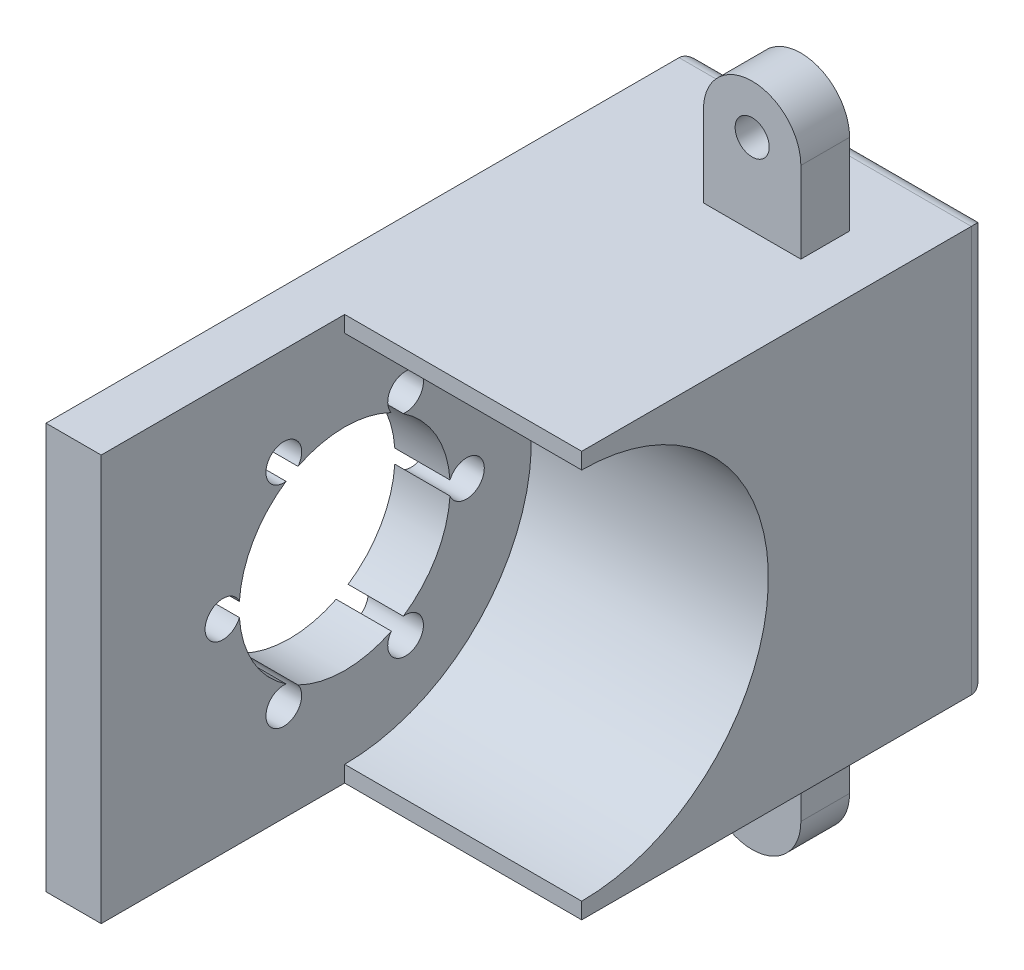
SolidWorks part; units mm, degrees
ref_plane "前视基准面" through (0, 0, 0) normal (0, 0, 1) x (1, 0, 0)
ref_plane "上视基准面" through (0, 0, 0) normal (0, 1, 0) x (1, 0, 0)
ref_plane "右视基准面" through (0, 0, 0) normal (1, 0, 0) x (0, 0, -1)
sketch "草图1" plane through (0, 0, 0) normal (0, 0, 1) x (1, 0, 0)
  line L9 (-11.5, 12.5) -> (11.5, 12.5)
  line L10 (-11.5, 12.5) -> (-11.5, -12.5)
  line L11 (-11.5, -12.5) -> (11.5, -12.5)
  line L12 (11.5, 12.5) -> (11.5, -12.5)
  line L13 (0, -12.5) -> (0, 12.5) construction
  line L14 (-11.5, 0) -> (11.5, 0) construction
  point P0 (0, 0)
  dimension "D1" = 23
  dimension "D2" = 25
extrude "凸台-拉伸1" add sketch "草图1" against normal blind 25 contours L12 L9 L10 L11 region at (0, 0, 0)
ref_axis "基准轴2" through (11.5, 0, 0) along (-1, 0, 0)
sketch "草图2" plane through (0, 0, 0) normal (0, 0, 1) x (1, 0, 0)
  line L0 (11.5, 0) -> (-11.5, 0) construction
  line L1 (11.5, 12.5) -> (11.5, -12.5) construction
  line L2 (11.5, 12.5) -> (11.5, -12.5) construction
  line L3 (11.5, 0) -> (11.5, -11.5)
  line L4 (11.5, -11.5) -> (-8.1, -11.5)
  line L9 (-8.1, -11.5) -> (-8.1, 0)
  line L10 (11.5, 0) -> (-8.1, 0)
  dimension "D1" = 11.5
  dimension "D2" = 19.6
revolve "切除-旋转2" cut sketch "草图2" angle 360 about axis through (11.5, 0, 0) along (-1, 0, 0)
ref_plane "基准面1" through (0, 0, 0) normal (0, 0, 1) x (1, 0, 0)
sketch "草图4" plane through (0, 0, 0) normal (0, 0, 1) x (1, 0, 0)
  line L0 (-8.1, 12.5) -> (-8.1, -12.5)
  line L1 (-11.5, 12.5) -> (11.5, 12.5) construction
  line L2 (-8.1, -12.5) -> (-11.5, -12.5)
  line L3 (-11.5, -12.5) -> (-11.5, 12.5)
  line L4 (-11.5, 12.5) -> (-8.1, 12.5)
  line L5 (-8.1, -11.5) -> (-8.1, 11.5) construction
  line L6 (-8.1, -11.5) -> (-8.1, 10.9) construction
  dimension "D1" = 25
extrude "凸台-拉伸2" add sketch "草图4" along normal blind 15
ref_plane "基准面2" through (-8.1, 0, 0) normal (1, 0, 0) x (0, 0, -1)
sketch "草图6" plane through (-8.1, 0, 0) normal (1, 0, 0) x (0, 0, -1)
  line L0 (0, 0) -> (7.5, 0) construction
  circle A0 centre (0, 0) radius 7.5 construction
  circle A1 centre (7.5, 0) radius 1.1
  circle A2 centre (3.75, -6.4952) radius 1.1
  circle A3 centre (-3.75, -6.4952) radius 1.1
  circle A5 centre (0, 0) radius 6.5
  circle A6 centre (-7.5, 0) radius 1.1
  circle A7 centre (-3.75, 6.4952) radius 1.1
  circle A8 centre (3.75, 6.4952) radius 1.1
  point P12 (0, 0)
  dimension "D1" = 15
  dimension "D2" = 2.2
  dimension "D5" = 13
  dimension "D3" = 6
extrude "切除-拉伸1" cut sketch "草图6" against normal blind 4 contours A7 | A6 | A8 | A1 | A3 | A2 | A5 region at (-8.1, 0, -7.5159) region at (-8.1, 6.509, -3.758) region at (-8.1, -6.509, -3.758) region at (-8.1, 6.509, 3.758) region at (-8.1, -6.509, 3.758) region at (-8.1, 0, 7.5159)
sketch "草图8" plane through (0, 0, -25) normal (0, 0, -1) x (-1, 0, 0)
  line L0 (11.5, -12.5) -> (-11.5, -12.5) construction
  line L1 (0, -1026.5) -> (0, -20.5) construction
  line L2 (11.5, 0) -> (2.7493, 0) construction
  line L3 (3, 17.5) -> (3, 12.5)
  line L5 (-3, -17.5) -> (-3, -12.5)
  line L6 (-3, -12.5) -> (3, -12.5)
  line L7 (3, -17.5) -> (3, -12.5)
  line L8 (-3, 17.5) -> (-3, 12.5)
  line L9 (-3, -15) -> (3, -15) construction
  line L10 (0, -12.5) -> (0, 0) construction
  line L11 (-3, 12.5) -> (3, 12.5)
  line L19 (11.5, 0) -> (16.5, 0) construction
  arc A0 (-3, -17.5) -> (3, -17.5) centre (0, -17.5) ccw
  circle A1 centre (0, -17.5) radius 1.05
  arc A2 (-3, 17.5) -> (3, 17.5) centre (0, 17.5) cw
  circle A3 centre (0, 17.5) radius 1.05
  point P5 (0, -15)
  point P28 (0, -12.5)
  dimension "D3" = 3
  dimension "D4" = 2.1
  dimension "D1" = 5
  dimension "D2" = 6
extrude "凸台-拉伸3" add sketch "草图8" against normal blind 8
extrude "切除-拉伸4" cut sketch "草图8<2>" against normal blind 5
sketch "草图8<2>" plane through (0, 0, -25) normal (0, 0, -1) x (-1, 0, 0) same geometry as "草图8"
sketch "草图7" plane through (11.5, 0, 0) normal (1, 0, 0) x (0, 0, -1)
  line L1 (-6, -20) -> (29, -20)
  line L2 (-6, -20) -> (-6, 20)
  line L3 (-6, 20) -> (29, 20)
  line L4 (29, -20) -> (29, 20)
  line L5 (11.5, 20) -> (11.5, -20) construction
  line L6 (-6, 0) -> (29, 0) construction
  arc A0 (0, -11.5) -> (0, 11.5) centre (0, 0) ccw construction
  point P4 (11.5, 0)
  dimension "D1" = 40
  dimension "D2" = 35
extrude "切除-拉伸3" cut sketch "草图7" against normal blind 5
fillet "圆角1" radius 1 4 edges at (-2.5, -12.5, -25) (-11.5, 0, -25) (-2.5, 12.5, -25) (6.5, 0, -25)
